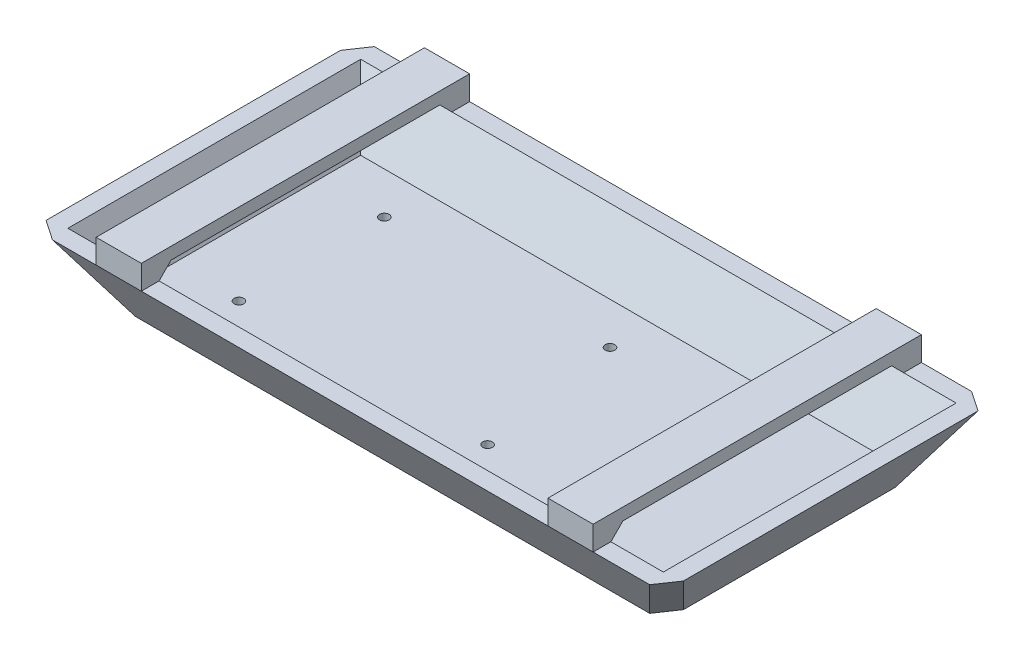
SolidWorks part; units mm, degrees
ref_plane "Front Plane" through (0, 0, 0) normal (0, 0, 1) x (1, 0, 0)
ref_plane "Top Plane" through (0, 0, 0) normal (0, 1, 0) x (1, 0, 0)
ref_plane "Right Plane" through (0, 0, 0) normal (1, 0, 0) x (0, 0, -1)
sketch "Sketch1" plane through (0, 0, 0) normal (0, 1, 0) x (1, 0, 0)
  line L1 (-91, -40.75) -> (91, -40.75)
  line L2 (-91, -40.75) -> (-91, 40.75)
  line L3 (-91, 40.75) -> (91, 40.75)
  line L4 (91, -40.75) -> (91, 40.75)
  line L5 (-91, -40.75) -> (91, 40.75) construction
  line L6 (-91, 40.75) -> (91, -40.75) construction
  point P0 (0, 0)
  dimension "D1" = 182
  dimension "D2" = 81.5
extrude "Boss-Extrude1" add sketch "Sketch1" along normal blind 22 draft 32 draft outward yes
shell "Shell1" thickness 5
sketch "Sketch2" plane through (0, 5, 0) normal (0, 1, 0) x (1, 0, 0)
  line L0 (88.2285, 37.9785) -> (-88.2285, 37.9785) construction
  line L1 (-88.2285, -37.9785) -> (88.2285, -37.9785) construction
  line L2 (-88.2285, 37.9785) -> (-88.2285, -37.9785) construction
  circle A0 centre (-66.5235, 24.1385) radius 1.6
  circle A1 centre (-66.5235, -24.1415) radius 1.6
  circle A2 centre (8.4065, 24.1385) radius 1.6
  circle A3 centre (16.0265, -24.1415) radius 1.6
  circle A4 centre (46.5065, 14.6185) radius 1.6
  dimension "D1" = 48.28
  dimension "D3" = 48.28
  dimension "D4" = 74.93
  dimension "D5" = 82.55
  dimension "D7" = 13.8369
  dimension "D8" = 21.705
  dimension "D9" = 38.1
  dimension "D10" = 9.52
  dimension "D2" = 0
  dimension "D6" = 13.84
extrude "Cut-Extrude1" cut sketch "Sketch2" against normal blind 22
chamfer "Chamfer1" distance 4 angle 45 4 edges at (97.8736, 11, 47.6236) (97.8736, 11, -47.6236) (-97.8736, 11, -47.6236) (-97.8736, 11, 47.6236)
sketch "Sketch3" plane through (0, 22, 0) normal (0, 1, 0) x (1, 0, 0)
  line L0 (98.0796, 54.4971) -> (-100.2202, 54.4971) construction
  line L1 (-83.5702, 54.4971) -> (-68.5702, 54.4971)
  line L2 (-83.5702, 54.4971) -> (-83.5702, 48.6012)
  line L3 (-83.5702, 48.6012) -> (-68.5702, 48.6012)
  line L4 (-68.5702, 54.4971) -> (-68.5702, 48.6012)
  line L5 (98.8512, 48.6012) -> (-98.8512, 48.6012) construction
  line L6 (-98.8512, -48.6012) -> (98.8512, -48.6012) construction
  line L7 (66.4298, 54.4971) -> (81.4298, 54.4971)
  line L8 (66.4298, 54.4971) -> (66.4298, 48.6012)
  line L9 (66.4298, 48.6012) -> (81.4298, 48.6012)
  line L10 (81.4298, 54.4971) -> (81.4298, 48.6012)
  line L11 (-83.5702, -48.6012) -> (-68.5702, -48.6012)
  line L12 (-83.5702, -48.6012) -> (-83.5702, -54.4971)
  line L13 (-83.5702, -54.4971) -> (-68.5702, -54.4971)
  line L14 (-68.5702, -48.6012) -> (-68.5702, -54.4971)
  line L15 (-98.0796, -54.4971) -> (100.2202, -54.4971) construction
  line L17 (66.4298, -48.6012) -> (81.4298, -48.6012)
  line L18 (66.4298, -48.6012) -> (66.4298, -54.4971)
  line L19 (66.4298, -54.4971) -> (81.4298, -54.4971)
  line L20 (81.4298, -48.6012) -> (81.4298, -54.4971)
  dimension "D1" = 165
  dimension "D2" = 15
  dimension "D3" = 15
  dimension "D4" = 16.65
  dimension "D5" = 165
  dimension "D6" = 0
  dimension "D7" = 15
  dimension "D8" = 15
extrude "Boss-Extrude2" add sketch "Sketch3" along normal blind 8
sketch "Sketch6" plane through (0, 0, 48.6012) normal (0, 0, -1) x (-1, 0, 0)
  line L0 (-66.4298, 30) -> (-66.4298, 22) construction
  line L1 (-81.4298, 30) -> (-66.4298, 30)
  line L2 (-81.4298, 30) -> (-81.4298, 26)
  line L3 (-81.4298, 26) -> (-66.4298, 26)
  line L4 (-66.4298, 30) -> (-66.4298, 26)
  dimension "D1" = 4
extrude "Boss-Extrude3" add sketch "Sketch6" along normal blind 98
sketch "Sketch7" plane through (0, 0, 48.6012) normal (0, 0, -1) x (-1, 0, 0)
  line L0 (83.5702, 30) -> (83.5702, 22) construction
  line L1 (68.5702, 30) -> (83.5702, 30)
  line L2 (68.5702, 30) -> (68.5702, 26)
  line L3 (68.5702, 26) -> (83.5702, 26)
  line L4 (83.5702, 30) -> (83.5702, 26)
  dimension "D1" = 4
extrude "Boss-Extrude4" add sketch "Sketch7" along normal blind 98
chamfer "Chamfer2" distance 4 angle 45 4 edges at (-76.0702, 26, 48.6012) (-76.0702, 26, -48.6012) (73.9298, 26, 48.6012) (73.9298, 26, -48.6012)
